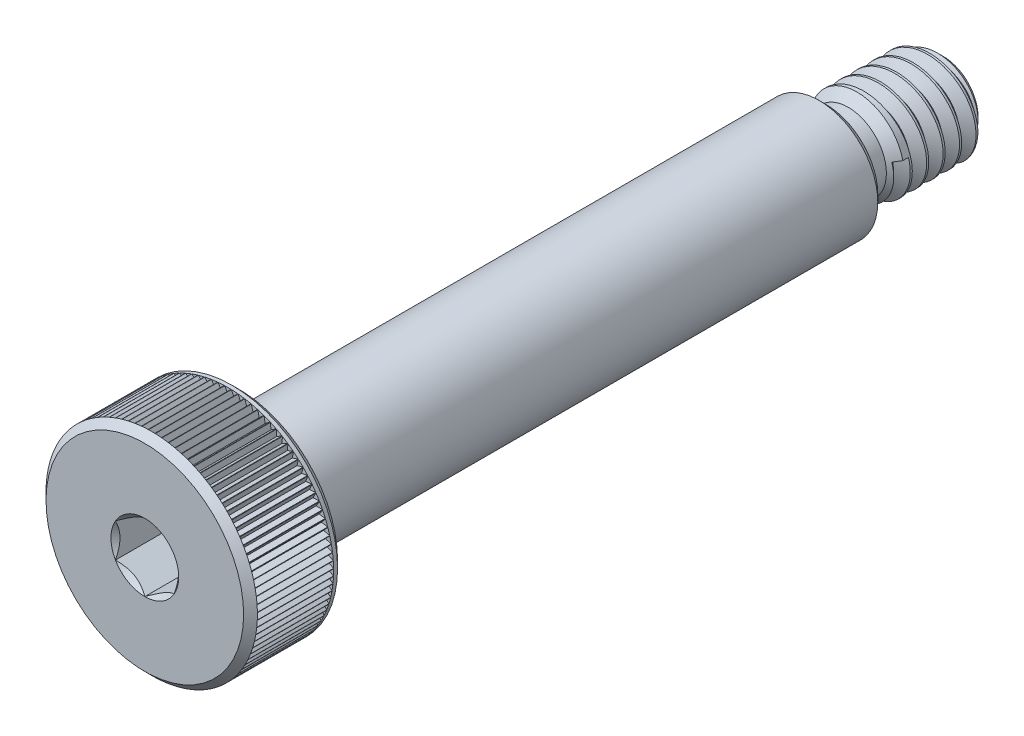
SolidWorks part; units mm, degrees
ref_plane "Front Plane" through (0, 0, 0) normal (0, 0, 1) x (1, 0, 0)
ref_plane "Top Plane" through (0, 0, 0) normal (0, 1, 0) x (1, 0, 0)
ref_plane "Right Plane" through (0, 0, 0) normal (1, 0, 0) x (0, 0, -1)
sketch "Sketch1" plane through (0, 0, 0) normal (1, 0, 0) x (0, 0, -1)
  line L0 (-17, 0) -> (17, 0) construction
  line L1 (-17, -4.5) -> (-17, 4.5) construction
  line L2 (-17, 4.5) -> (-13, 4.5) construction
  line L3 (-13, 4.5) -> (-13, 2.297) construction
  line L4 (-13, 2.297) -> (-12.492, 2.297) construction
  line L5 (-12.492, 2.297) -> (-12.289, 2.5) construction
  line L6 (-12.289, 2.5) -> (12, 2.5) construction
  line L7 (16.9563, 2.0758) -> (17.3063, 1.4696) construction
  line L8 (17.3063, 1.4696) -> (17.6563, 2.0758) construction
  line L9 (17, -2) -> (17, 2) construction
  line L10 (12, 2.5) -> (17, 2.5) construction
  line L11 (17.6563, 2.0758) -> (16.9563, 2.0758) construction
  line L12 (17.3063, 2.0758) -> (17.3063, 2) construction
  line L13 (17.3063, 1.4696) -> (17.3063, 1.5453) construction
  line L14 (17.35, 1.5453) -> (17.2625, 1.5453) construction
  line L15 (17.6125, 2) -> (17, 2) construction
  line L16 (17.3063, 2.0379) -> (17.6344, 2.0379) construction
  line L17 (17.3063, 2.0379) -> (16.9781, 2.0379) construction
  line L18 (-17, 4.2075) -> (-16.7075, 4.5) construction
  line L19 (-13.2925, 4.5) -> (-13, 4.2075) construction
  line L20 (17, 2) -> (12, 2) construction
  line L21 (16.475, 2) -> (17, 1.475) construction
  line L22 (13.325, 2) -> (12.95, 1.625) construction
  line L23 (12.95, 1.625) -> (12.1875, 1.625) construction
  line L24 (12, 2) -> (12, 1.8125) construction
  line L25 (-15, 1.25) -> (-15, -1.25) construction
  line L26 (-15, -1.25) -> (-17, -1.25) construction
  line L27 (-15, 1.25) -> (-17, 1.25) construction
  line L28 (-16.7075, 0) -> (-13.4633, 0) construction
  arc A0 (12, 1.8125) -> (12.1875, 1.625) centre (12.1875, 1.8125) ccw construction
  point P4 (0, 0)
  point P7 (-17, 0)
  point P18 (17, 0)
  point P25 (14.55, -2)
  point P38 (-15, 4.5)
  point P45 (-15, 0)
  point P46 (13.1375, 1.8125)
  point P48 (-12.492, 0)
  point P51 (-15, 0)
  point P52 (12, 0)
  point P53 (-9.8, 0)
  dimension "Head Diameter" = 9
  dimension "Head Height" = 4
  dimension "Thread Diameter" = 4
  dimension "Shoulder Diameter" = 5
  dimension "Thread Length" = 5
  dimension "D1" = 0.508
  dimension "D2" = 135
  dimension "D3" = 0.203
  dimension "Shoulder Length" = 25
  dimension "Thread Pitch" = 0.7
  dimension "D4" = 0.0875
  dimension "D5" = 2.45
  dimension "D6" = 0.2925
  dimension "D7" = 0.525
  dimension "D8" = 3.25
  dimension "D9" = 0.95
  dimension "Drive Size" = 2.5
  dimension "Knurling Length" = 3.2443
  dimension "D10" = 7.2
sketch "Sketch3" plane through (0, 0, 0) normal (1, 0, 0) x (0, 0, -1)
  line L0 (-17, 0) -> (-17, 4.2075)
  line L1 (-17, -4.5) -> (-17, 4.5) construction
  line L2 (-17, 4.2075) -> (-16.7075, 4.5)
  line L3 (-16.7075, 4.5) -> (-13.2925, 4.5)
  line L4 (-13.2925, 4.5) -> (-13, 4.2075)
  line L5 (-13, 4.2075) -> (-13, 2.297)
  line L6 (-13, 2.297) -> (-12.492, 2.297)
  line L7 (-12.492, 2.297) -> (-12.289, 2.5)
  line L8 (-12.289, 2.5) -> (12, 2.5)
  line L9 (12, 2.5) -> (12, 1.8125)
  line L10 (12.1875, 1.625) -> (12.95, 1.625)
  line L11 (12.95, 1.625) -> (13.325, 2)
  line L12 (13.325, 2) -> (16.475, 2)
  line L13 (16.475, 2) -> (17, 1.475)
  line L14 (17, 1.475) -> (17, 0)
  line L15 (17, 0) -> (-17, 0)
  arc A0 (12, 1.8125) -> (12.1875, 1.625) centre (12.1875, 1.8125) ccw construction
  arc A1 (12, 1.8125) -> (12.1875, 1.625) centre (12.1875, 1.8125) ccw
revolve "Revolve1" add sketch "Sketch3" angle 360 about L0
sketch "Sketch4" plane through (0, 0, 0) normal (0, 0, 1) x (1, 0, 0)
  line L0 (0, -4.5) -> (0, 4.5) construction
  line L1 (0, 1.4434) -> (-1.25, 0.7217)
  line L2 (-1.25, 0.7217) -> (-1.25, -0.7217)
  line L3 (-1.25, -0.7217) -> (0, -1.4434)
  line L4 (0, -1.4434) -> (1.25, -0.7217)
  line L5 (1.25, -0.7217) -> (1.25, 0.7217)
  line L6 (1.25, 0.7217) -> (0, 1.4434)
  circle A0 centre (0, 0) radius 1.25 construction
extrude "Cut-Extrude1" cut sketch "Sketch4" against normal up to vertex (-15 mm away) from vertex up to point (0, 0, 15) starting at point (0, 0, 17)
sketch "Sketch5" plane through (0, 0, 0) normal (0, 0, 1) x (1, 0, 0)
  line L0 (0, -4.5) -> (0, 4.5) construction
  circle A0 centre (0, 0) radius 1.4434
extrude "Cut-Extrude2" cut sketch "Sketch5" against normal up to vertex (-15 mm away) draft 45 from vertex up to point (0, 0, 15) starting at point (0, 0, 17)
chamfer "Chamfer1" distance 0.2925 angle 45 1 edges at (2.5, 0, -12)
sketch "Sketch6" plane through (0, 0, -17) normal (0, 0, -1) x (-1, 0, 0)
  circle A0 centre (0, 0) radius 2
curve "Helix/Spiral1" pitch 0.7 height 4.05 radius 2 centre (0, 0, -17) axis (0, 0, 1) start towards (0, 1, 0)
sketch "Sketch7" plane through (0, 0, 0) normal (1, 0, 0) x (0, 0, -1)
  line L0 (16.9781, 2.0379) -> (17.2625, 1.5453)
  line L1 (17.2625, 1.5453) -> (17.35, 1.5453)
  line L2 (17.35, 1.5453) -> (17.6344, 2.0379)
  line L3 (17.6344, 2.0379) -> (16.9781, 2.0379)
sweep "Cut-Sweep1" cut profiles "Sketch7" path "Helix/Spiral1"
sketch "Sketch8" plane through (0, 0, 0) normal (0, 0, 1) x (1, 0, 0)
  line L0 (0, 4.5) -> (0, 0) construction
  line L1 (-0.1351, 4.5) -> (0.1351, 4.5)
  line L2 (0.1351, 4.5) -> (0, 4.266)
  line L3 (0, 4.266) -> (-0.1351, 4.5)
  line L4 (-0.1351, 4.5) -> (0, 0) construction
  line L5 (0, 0) -> (0.1351, 4.5) construction
  circle A0 centre (0, 0) radius 4.266 construction
  point P8 (0, 4.5)
  dimension "D1" = 0.234
  dimension "D2" = 3.439
extrude "Cut-Extrude3" cut sketch "Sketch8" against normal up to vertex (-13.4633 mm away) from vertex up to point (0, 0, 13.4633) starting at point (0, 0, 16.7075)
pattern_circular "CirPattern1" count 99 over 360 about axis through (0, 0, 17) along (0, 0, -1) of "Cut-Extrude3"
equation "\"D4@Sketch1\"=\"Thread Pitch@Sketch1\"/8"
equation "\"D5@Sketch1\"=\"Thread Pitch@Sketch1\"*3.5"
equation "\"D6@Sketch1\"=\"Head Diameter@Sketch1\"*.0325"
equation "\"D7@Sketch1\"=\"Thread Pitch@Sketch1\"*.75"
equation "\"D1@Chamfer1\"=\"D6@Sketch1\""
equation "\"D4@Helix/Spiral1\"=\"Thread Pitch@Sketch1\""
equation "\"D3@Helix/Spiral1\" = \"Thread Length@Sketch1\" - \"D9@Sketch1\""
equation "\"D1@Sketch8\"=\"D6@Sketch1\"*.8"
equation "\"D1@CirPattern1\"=(360/\"D2@Sketch8\")-6"
equation "\"D9@Sketch1\"  = \"Thread Length@Sketch1\"*.2"
equation "\"D8@Sketch1\"=\"Thread Diameter@Sketch1\"*.65"
equation "\"D10@Sketch1\"=\"Head Diameter@Sketch1\"*.8"
